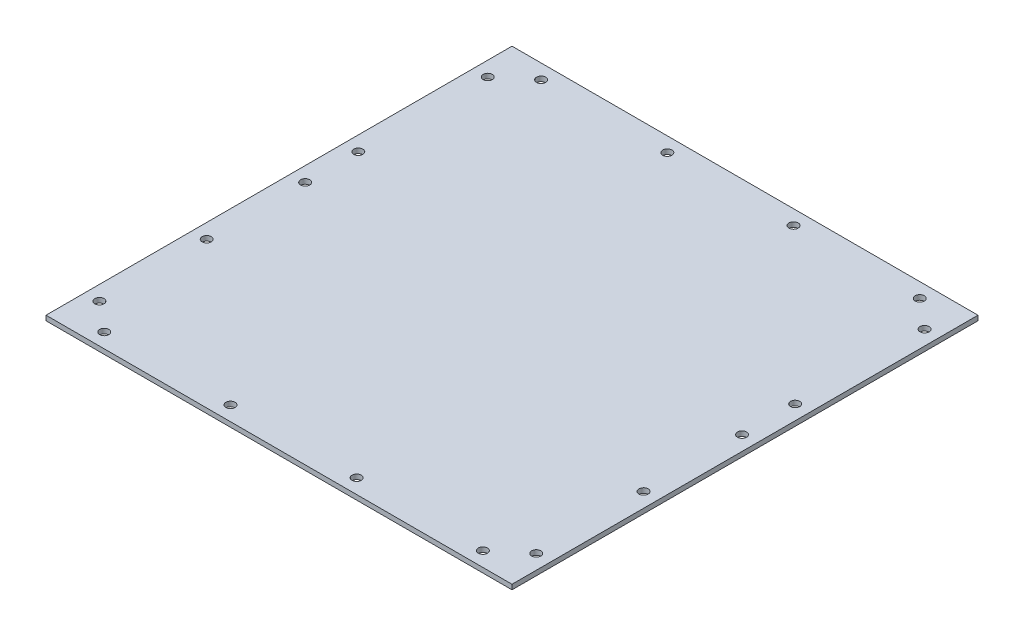
SolidWorks part; units mm, degrees
ref_plane "Front Plane" through (0, 0, 0) normal (0, 0, 1) x (1, 0, 0)
ref_plane "Top Plane" through (0, 0, 0) normal (0, 1, 0) x (1, 0, 0)
ref_plane "Right Plane" through (0, 0, 0) normal (1, 0, 0) x (0, 0, -1)
sketch "Sketch2" plane through (0, 0, 0) normal (0, 1, 0) x (1, 0, 0)
  line L0 (0, 0) -> (152.4, 0)
  line L1 (152.4, 0) -> (152.4, 152.4)
  line L2 (152.4, 152.4) -> (0, 152.4)
  line L3 (0, 152.4) -> (0, 0)
  dimension "D1" = 152.4
  dimension "D2" = 152.4
extrude "Boss-Extrude1" add sketch "Sketch2" along normal blind 1.5875
sketch "Sketch3" plane through (0, 1.5875, 0) normal (0, 1, 0) x (1, 0, 0)
  line L0 (0, 152.4) -> (4.7625, 152.4)
  line L1 (152.4, 152.4) -> (0, 152.4) construction
  line L2 (4.7625, 152.4) -> (4.7625, 0)
  line L3 (0, 0) -> (152.4, 0) construction
  line L4 (0, 152.4) -> (0, 147.6375)
  line L5 (0, 152.4) -> (0, 0) construction
  line L6 (0, 147.6375) -> (152.4, 147.6375)
  line L7 (152.4, 0) -> (152.4, 152.4) construction
  line L8 (152.4, 152.4) -> (147.6375, 152.4)
  line L9 (147.6375, 152.4) -> (147.6375, 0)
  line L10 (152.4, 0) -> (152.4, 4.7625)
  line L11 (152.4, 4.7625) -> (0, 4.7625)
  point P21 (4.7625, 139.7)
  point P23 (14.2875, 147.6375)
  point P24 (147.6375, 139.7)
  point P25 (138.1125, 4.7625)
  point P26 (4.7625, 12.7)
  dimension "D1" = 4.7625
  dimension "D2" = 4.7625
  dimension "D3" = 4.7625
  dimension "D4" = 4.7625
  dimension "D5" = 12.7
  dimension "D6" = 14.2875
  dimension "D7" = 12.7
  dimension "D8" = 14.2875
  dimension "D9" = 12.7
sketch "Sketch4" plane through (0, 1.5875, 0) normal (0, 1, 0) x (1, 0, 0)
  point P0 (14.2875, 147.6375)
  point P3 (147.6375, 139.7)
  point P6 (138.1125, 4.7625)
  point P9 (4.7625, 12.7)
sketch "Sketch6" plane through (0, 1.5875, 0) normal (0, 1, 0) x (1, 0, 0)
  line L0 (152.4, 4.7625) -> (0, 4.7625) construction
  line L1 (0, 152.4) -> (0, 0) construction
  point P0 (14.2875, 147.6375)
  point P3 (14.2875, 4.7625)
  dimension "D1" = 14.2875
hole_wizard "Ø3.0mm Dowel Hole2" positions "Sketch6" profile "Sketch7" hole size "Ø3.0" standard "ANSI Metric" end condition through all
sketch "Sketch7" plane through (14.2875, 1.5875, -147.6375) normal (1, 0, 0) x (0, 0, 1)
  line L0 (0, 0) -> (0, 1.5875)
  line L1 (0, 1.5875) -> (1.5, 1.5875)
  line L2 (1.5, 1.5875) -> (1.5, 0)
  line L5 (1.5, 0) -> (0, 0)
  line L11 (0, -6.35) -> (0, 107.95) construction
  dimension "Thru Hole Dia." = 3
  dimension "Thru Hole Depth" = 1.5875
sketch "Sketch8" plane through (0, 1.5875, 0) normal (0, 1, 0) x (1, 0, 0)
  point P0 (4.7625, 139.7)
  point P3 (147.6375, 139.7)
hole_wizard "Ø3.0mm Dowel Hole3" positions "Sketch8" profile "Sketch9" hole size "Ø3.0" standard "ANSI Metric" end condition through all
sketch "Sketch9" plane through (4.7625, 1.5875, -139.7) normal (1, 0, 0) x (0, 0, 1)
  line L0 (0, 0) -> (0, 1.5875)
  line L1 (0, 1.5875) -> (1.5, 1.5875)
  line L2 (1.5, 1.5875) -> (1.5, 0)
  line L5 (1.5, 0) -> (0, 0)
  line L11 (0, -6.35) -> (0, 107.95) construction
  dimension "Thru Hole Dia." = 3
  dimension "Thru Hole Depth" = 1.5875
pattern_linear "LPattern1" count 4 spacing 42.3333 along (0, 0, 1) skipping (2, 0) of "Ø3.0mm Dowel Hole3"
pattern_linear "LPattern2" count 4 spacing 41.275 along (1, 0, 0) of "Ø3.0mm Dowel Hole2"
sketch "Sketch10" plane through (0, 1.5875, 0) normal (0, 1, 0) x (1, 0, 0)
  line L1 (0, 0) -> (152.4, 0) construction
  point P1 (147.6375, 47.79)
  point P5 (147.6375, 80)
  dimension "D1" = 32.21
  dimension "D2" = 80
hole_wizard "Ø3.0mm Dowel Hole1" positions "Sketch10" profile "Sketch11" hole size "Ø3.0" standard "ANSI Metric" end condition through all
sketch "Sketch11" plane through (147.6375, 1.5875, -47.79) normal (1, 0, 0) x (0, 0, 1)
  line L0 (0, 0) -> (0, 1.5875)
  line L1 (0, 1.5875) -> (1.5, 1.5875)
  line L2 (1.5, 1.5875) -> (1.5, 0)
  line L5 (1.5, 0) -> (0, 0)
  line L11 (0, -6.35) -> (0, 107.95) construction
  dimension "Thru Hole Dia." = 3
  dimension "Thru Hole Depth" = 1.5875
ref_plane "Plane1" through (76.2, 0, 0) normal (1, 0, 0) x (0, 0, -1)
mirror "Mirror1" about plane through (76.2, 0, 0) normal (1, 0, 0) of "Ø3.0mm Dowel Hole1"
